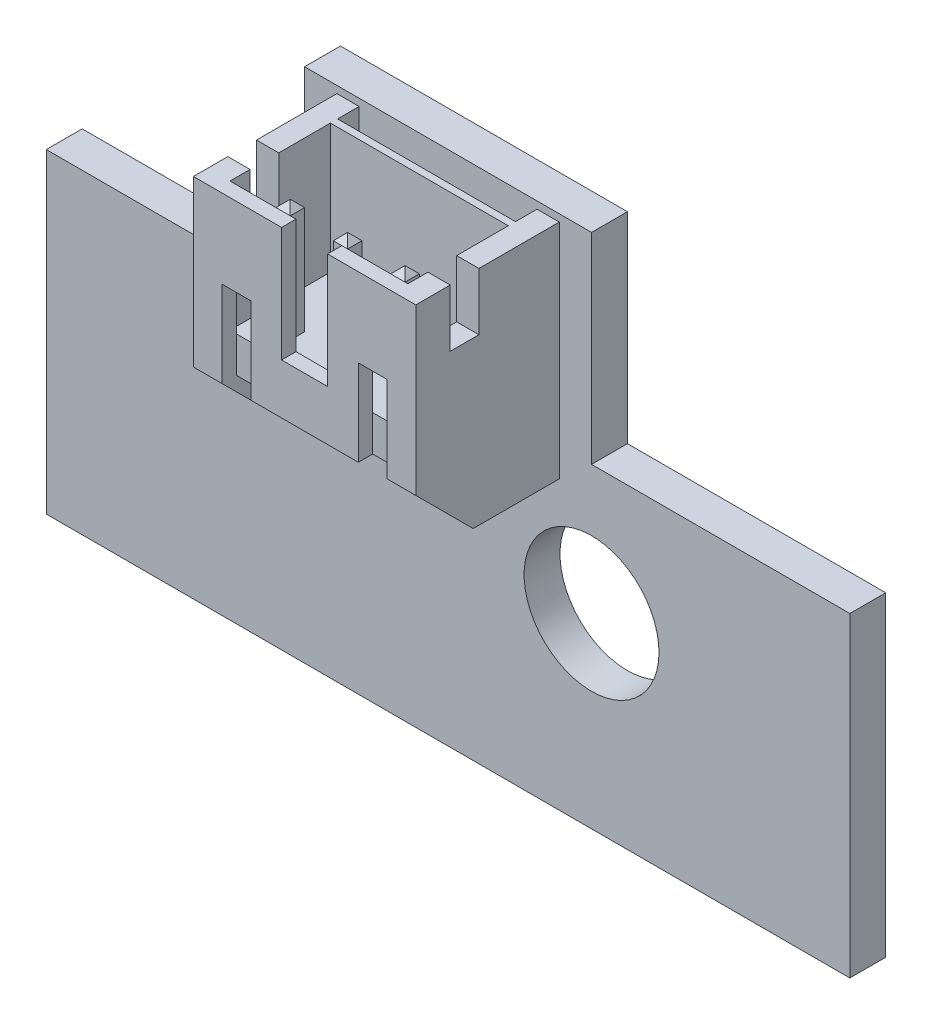
SolidWorks part; units mm, degrees
ref_plane "Alzado" through (0, 0, 0) normal (0, 0, 1) x (1, 0, 0)
ref_plane "Planta" through (0, 0, 0) normal (0, 1, 0) x (1, 0, 0)
ref_plane "Vista lateral" through (0, 0, 0) normal (1, 0, 0) x (0, 0, -1)
sketch "Croquis1" plane through (0, 0, 0) normal (0, 0, 1) x (1, 0, 0)
  line L1 (14, -5.5) -> (-14, -5.5)
  line L2 (14, -5.5) -> (14, 5.5)
  line L3 (14, 5.5) -> (-14, 5.5)
  line L4 (-14, -5.5) -> (-14, 5.5)
  line L5 (14, -5.5) -> (-14, 5.5) construction
  line L6 (14, 5.5) -> (-14, -5.5) construction
  line L7 (5, -1.5) -> (-5, -1.5)
  line L8 (5, -1.5) -> (5, 12.5)
  line L9 (5, 12.5) -> (-5, 12.5)
  line L10 (-5, -1.5) -> (-5, 12.5)
  line L11 (5, -1.5) -> (-5, 12.5) construction
  line L12 (5, 12.5) -> (-5, -1.5) construction
  circle A0 centre (5, 1) radius 2.35
  point P0 (0, 0)
  point P6 (0, 5.5)
  dimension "D5" = 4.7
  dimension "D1" = 28
  dimension "D2" = 11
  dimension "D3" = 10
  dimension "D4" = 7
  dimension "D6" = 6.5
  dimension "D7" = 9
extrude "Extruir1" add sketch "Croquis1" along normal blind 1.25 contours A0 L8 L7 L10 L3 L4 L1 L2 | L10 L3 L8 L9 | A0 L8 L3 L10 L7
sketch "Croquis2" plane through (0, 0, 1.25) normal (0, 0, 1) x (1, 0, 0)
  line L1 (0, 12.5) -> (0, 0) construction
  line L2 (5, 12.5) -> (-5, 12.5) construction
  line L4 (3.875, 4.5) -> (-3.875, 4.5)
  line L5 (3.875, 4.5) -> (3.875, 12.25)
  line L6 (3.875, 12.25) -> (-3.875, 12.25)
  line L8 (-3.875, 4.5) -> (-3.875, 12.25)
  line L9 (3.875, 4.5) -> (-3.875, 12.25) construction
  line L10 (3.875, 12.25) -> (-3.875, 4.5) construction
  point P4 (0, 8.375)
  dimension "D1" = 7.75
  dimension "D2" = 0.25
  dimension "D3" = 7.75
extrude "Extruir2" add sketch "Croquis2" along normal blind 5
sketch "Croquis3" plane through (0, 12.25, 0) normal (0, 1, 0) x (-1, 0, 0)
  line L0 (-3.875, 6.25) -> (3.875, 6.25) construction
  line L1 (3.0998, 2.25) -> (-3.0998, 2.25)
  line L2 (3.0998, 2.25) -> (3.0998, 5.75)
  line L3 (3.0998, 5.75) -> (-3.0998, 5.75)
  line L4 (-3.0998, 2.25) -> (-3.0998, 5.75)
  line L5 (3.0998, 2.25) -> (-3.0998, 5.75) construction
  line L6 (3.0998, 5.75) -> (-3.0998, 2.25) construction
  point P0 (0, 4)
  dimension "D1" = 0.5
  dimension "D2" = 3.5
extrude "Extruir3" cut sketch "Croquis3" against normal blind 4.5
sketch "Croquis4" plane through (0, 0, 6.25) normal (0, 0, 1) x (1, 0, 0)
  line L0 (-3.875, 4.5) -> (3.875, 4.5) construction
  line L1 (2.875, 4.5) -> (-2.875, 4.5)
  line L2 (2.875, 4.5) -> (2.875, 6.5)
  line L3 (2.875, 6.5) -> (-2.875, 6.5)
  line L4 (-2.875, 4.5) -> (-2.875, 6.5)
  line L5 (-3.875, 12.25) -> (-3.875, 4.5) construction
  line L6 (3.875, 4.5) -> (3.875, 12.25) construction
  dimension "D1" = 1
  dimension "D2" = 1
  dimension "D3" = 2
extrude "Extruir4" cut sketch "Croquis4" against normal blind 5
chamfer "Chaflán1" distance 2 angle 45 2 edges at (3.375, 4.5, 6.25) (-3.375, 4.5, 6.25)
sketch "Croquis5" plane through (0, 12.25, 0) normal (0, 1, 0) x (-1, 0, 0)
  line L0 (-3.875, 1.25) -> (3.875, 1.25) construction
  line L1 (-3.0998, 1.25) -> (3.0998, 1.25)
  line L2 (-3.0998, 1.25) -> (-3.0998, 2)
  line L3 (-3.0998, 2) -> (3.0998, 2)
  line L4 (3.0998, 1.25) -> (3.0998, 2)
  line L5 (-3.0998, 2.25) -> (3.0998, 2.25) construction
  dimension "D1" = 0.25
extrude "Extruir5" cut sketch "Croquis5" along direction (0, 1, 0) on the side against the normal up to surface (5.75 mm away)
sketch "Croquis6" plane through (0, 0, 6.25) normal (0, 0, 1) x (1, 0, 0)
  line L0 (3.875, 12.25) -> (-3.875, 12.25) construction
  line L1 (0.8, 12.25) -> (-0.8, 12.25)
  line L2 (0, 12.25) -> (0, 8.25)
  line L3 (0.8, 8.25) -> (-0.8, 8.25)
  line L4 (-0.8, 12.25) -> (-0.8, 8.25)
  line L5 (0, 11.6584) -> (0, 6.7358) construction
  line L6 (-2.875, 6.5) -> (-1.875, 6.5)
  line L7 (-2.875, 6.5) -> (-2.875, 9.5)
  line L8 (-2.875, 9.5) -> (-1.875, 9.5)
  line L9 (-1.875, 6.5) -> (-1.875, 9.5)
  line L10 (1.875, 6.5) -> (1.875, 9.5)
  line L11 (2.875, 9.5) -> (1.875, 9.5)
  line L12 (2.875, 6.5) -> (2.875, 9.5)
  line L13 (2.875, 6.5) -> (1.875, 6.5)
  line L14 (0.8, 12.25) -> (0.8, 8.25)
  line M1 (-2.875, 6.5) -> (2.875, 6.5)
  line M4 (3.875, 12.25) -> (-3.875, 12.25)
  dimension "D1" = 0.8
  dimension "D2" = 4
  dimension "D3" = 1
  dimension "D4" = 3
extrude "Extruir6" cut sketch "Croquis6" against normal up to surface (0.5 mm away) contours L9 L8 L7 M1 | L14 L2 L3 M4 | L1 L4 L3 L2 | L12 L11 L10 M1 up to face at (0, 10, 5.75)
sketch "Croquis7" plane through (3.875, 0, 0) normal (1, 0, 0) x (0, 0, -1)
  line L0 (-6.25, 12.25) -> (-1.25, 12.25) construction
  line L1 (-5.05, 12.25) -> (-4.05, 12.25)
  line L2 (-5.05, 12.25) -> (-5.05, 10.25)
  line L3 (-5.05, 10.25) -> (-4.05, 10.25)
  line L4 (-4.05, 12.25) -> (-4.05, 10.25)
  line L5 (-6.25, 6.5) -> (-6.25, 12.25) construction
  dimension "D1" = 1.2
  dimension "D2" = 2
  dimension "D3" = 1
extrude "Extruir7" cut sketch "Croquis7" against normal up to surface (7.75 mm away) up to face at (-3.875, 8, 3.85)
sketch "Croquis8" plane through (0, 7.75, 0) normal (0, 1, 0) x (-1, 0, 0)
  line L0 (0, 2.25) -> (0, 5.3424) construction
  line L1 (-3.0998, 2.25) -> (3.0998, 2.25) construction
  line L2 (-2.8019, 4.75) -> (2.3794, 4.75) construction
  line L3 (1.875, 5.75) -> (-1.875, 5.75) construction
  line L5 (0.25, 4.5) -> (-0.25, 4.5)
  line L6 (0.25, 4.5) -> (0.25, 5)
  line L7 (0.25, 5) -> (-0.25, 5)
  line L8 (-0.25, 4.5) -> (-0.25, 5)
  line L9 (0.25, 4.5) -> (-0.25, 5) construction
  line L10 (0.25, 5) -> (-0.25, 4.5) construction
  line L11 (2.25, 4.5) -> (1.75, 4.5)
  line L12 (2.25, 4.5) -> (2.25, 5)
  line L13 (2.25, 5) -> (1.75, 5)
  line L14 (1.75, 4.5) -> (1.75, 5)
  line L15 (2.25, 4.5) -> (1.75, 5) construction
  line L16 (2.25, 5) -> (1.75, 4.5) construction
  line L17 (-2.25, 4.5) -> (-1.75, 4.5)
  line L18 (-2.25, 4.5) -> (-2.25, 5)
  line L19 (-2.25, 5) -> (-1.75, 5)
  line L20 (-1.75, 4.5) -> (-1.75, 5)
  line L21 (-2.25, 4.5) -> (-1.75, 5) construction
  line L22 (-2.25, 5) -> (-1.75, 4.5) construction
  point P8 (0, 4.75)
  point P13 (2, 4.75)
  point P19 (-2, 4.75)
  dimension "D1" = 1
  dimension "D2" = 0.5
  dimension "D3" = 0.5
  dimension "D4" = 0.5
  dimension "D5" = 0.5
  dimension "D6" = 1.5
  dimension "D7" = 1.5
extrude "Extruir8" add sketch "Croquis8" along normal blind 4 and the other way blind 2.5
chamfer "Chaflán2" distance 0.25 angle 45 12 edges at (-2, 11.75, 5) (-2.25, 11.75, 4.75) (-2, 11.75, 4.5) (-1.75, 11.75, 4.75) (0, 11.75, 5) (-0.25, 11.75, 4.75) (0, 11.75, 4.5) (0.25, 11.75, 4.75) (2, 11.75, 4.5) (2.25, 11.75, 4.75) (2, 11.75, 5) (1.75, 11.75, 4.75)
sketch "Croquis9" plane through (0, 0, 5) normal (0, 0, 1) x (1, 0, 0)
  line L0 (-2.25, 5.25) -> (-2.25, 6.5) construction
  line L1 (-1.75, 5.25) -> (-2.25, 5.25)
  line L2 (-1.75, 5.25) -> (-1.75, 5.75)
  line L3 (-1.75, 5.75) -> (-2.25, 5.75)
  line L4 (-2.25, 5.25) -> (-2.25, 5.75)
  line L5 (0.25, 5.25) -> (0.25, 6.5) construction
  line L6 (-0.25, 5.25) -> (0.25, 5.25)
  line L7 (-0.25, 5.25) -> (-0.25, 5.75)
  line L8 (-0.25, 5.75) -> (0.25, 5.75)
  line L9 (0.25, 5.25) -> (0.25, 5.75)
  line L10 (1.75, 5.25) -> (1.75, 6.5) construction
  line L11 (1.75, 5.25) -> (2.25, 5.25)
  line L12 (1.75, 5.25) -> (1.75, 5.75)
  line L13 (1.75, 5.75) -> (2.25, 5.75)
  line L14 (2.25, 5.25) -> (2.25, 5.75)
  line L15 (2.25, 5.25) -> (2.25, 6.5) construction
  dimension "D1" = 0.5
extrude "Extruir9" add sketch "Croquis9" against normal blind 5.75
chamfer "Chaflán3" distance 0.25 angle 45 12 edges at (-2, 5.75, -0.75) (-2.25, 5.5, -0.75) (-2, 5.25, -0.75) (-1.75, 5.5, -0.75) (0, 5.25, -0.75) (0.25, 5.5, -0.75) (0, 5.75, -0.75) (-0.25, 5.5, -0.75) (2, 5.25, -0.75) (2.25, 5.5, -0.75) (2, 5.75, -0.75) (1.75, 5.5, -0.75)
